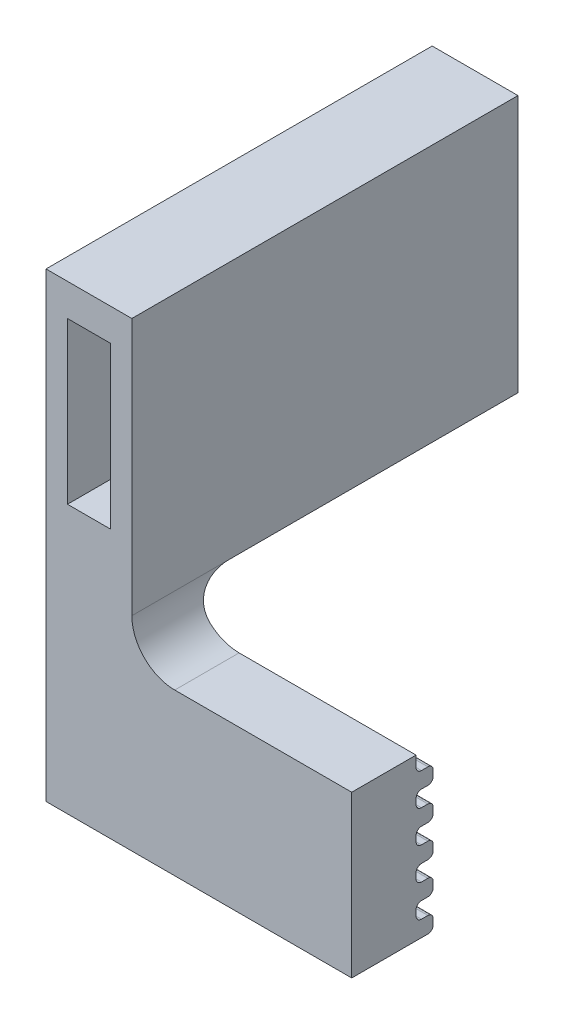
SolidWorks part; units mm, degrees
ref_plane "Спереди" through (0, 0, 0) normal (0, 0, 1) x (1, 0, 0)
ref_plane "Сверху" through (0, 0, 0) normal (0, 1, 0) x (1, 0, 0)
ref_plane "Справа" through (0, 0, 0) normal (1, 0, 0) x (0, 0, -1)
other "Configuration Table"
sketch "Эскиз1" plane through (0, 0, 0) normal (0, 0, 1) x (1, 0, 0)
  line L0 (4, 24) -> (4, 6) construction
  line L1 (2, 21) -> (6, 21)
  line L6 (2, 21) -> (2, 6)
  line L7 (2, 6) -> (6, 6)
  line L8 (6, 21) -> (6, 6)
  line L9 (0, 24) -> (8, 24)
  line L10 (0, 24) -> (0, 6)
  line L11 (0, 6) -> (8, 6)
  line L12 (8, 24) -> (8, 6)
  line L17 (8, 6) -> (8, 0)
  line L18 (0, 0) -> (0, 6)
  line L19 (0, 0) -> (8, 0)
  dimension "D1" = 4
  dimension "D3" = 0
  dimension "D4" = 8
  dimension "D5" = 6
  dimension "D6" = 15
  dimension "D7" = 3
extrude "Бобышка-Вытянуть1" add sketch "Эскиз1" along normal blind 8 contours L11 | L9 L0 L1 L8 L7 L12 | L0 L9 L10 L11 L7 L6 L1 | L17 region at (6.7143, 16.0714, 0) region at (1.2857, 16.0714, 0) region at (4, 3, 0)
extrude "Бобышка-Вытянуть2" add sketch "Эскиз1<3>" against normal blind 28 contours L9 L0 L1 L8 L7 L12 | L0 L9 L10 L11 L7 L6 L1 | L17 L11 region at (6.7143, 16.0714, 0) region at (1.2857, 16.0714, 0) region at (4, 3, 0)
sketch "Эскиз1<3>" plane through (0, 0, 0) normal (0, 0, 1) x (1, 0, 0) same geometry as "Эскиз1"
sketch "Эскиз3" plane through (0, 0, 0) normal (0, -1, 0) x (1, 0, 0)
  line L0 (5, -10) -> (-1, -10) construction
  line L1 (5, -11.5) -> (-1, -11.5)
  line L2 (5, -8.5) -> (-1, -8.5)
  line L3 (8, -10) -> (-27.6495, -10) construction
  line L4 (8, 8) -> (8, -28) construction
  line L6 (8, -6) -> (-4, -6)
  line L7 (8, -6) -> (8, -14)
  line L8 (8, -14) -> (-4, -14)
  line L9 (-4, -6) -> (-4, -14)
  arc A0 (5, -11.5) -> (5, -8.5) centre (5, -10) ccw
  arc A1 (-1, -8.5) -> (-1, -11.5) centre (-1, -10) ccw
  point P2 (2, -10)
  line M11 (0, 8) -> (0, -28)
  dimension "D1" = 3
  dimension "D2" = 6
  dimension "D3" = 3
  dimension "D4" = 8
  dimension "D5" = 12
extrude "Бобышка-Вытянуть4" add sketch "Эскиз3" against normal blind 6 contours A1 L2 L6 L9 L8 L1 M11 region at (-0.0894, 0, -12.75)
extrude "Вырез-Вытянуть2" cut sketch "Эскиз3<3>" against normal blind 6 contours L2 A1 L1 M11 | L1 A0 L2 M11 region at (3.0981, 0, -10) region at (-1.1148, 0, -10)
sketch "Эскиз3<3>" plane through (0, 0, 0) normal (0, -1, 0) x (1, 0, 0) same geometry as "Эскиз3"
sketch "Эскиз4" plane through (0, 0, 8) normal (0, 0, 1) x (1, 0, 0)
  line L1 (0, 0) -> (8, 0)
  line L2 (0, 0) -> (0, -4)
  line L3 (0, -4) -> (8, -4)
  line L4 (8, 0) -> (8, -4)
  line L5 (0, -4) -> (28.5, -4)
  line L6 (0, -4) -> (0, -19)
  line L7 (0, -19) -> (28.5, -19)
  line L8 (28.5, -4) -> (28.5, -19)
  line M16 (0, 0) -> (8, 0)
  dimension "D1" = 28.5
  dimension "D2" = 4
  dimension "D3" = 15
extrude "Бобышка-Вытянуть5" add sketch "Эскиз4" against normal blind 6 contours L8 L5 L3 L6 L7 | L4 L2 L3 M16 region at (4, -2, 8) region at (14.25, -11.5, 8)
fillet "Скругление1" radius 2 4 edges at (0, 3, -14) (-4, 3, -14) (-4, 3, -6) (0, 3, -6)
fillet "Скругление2" radius 3 1 edges at (4, 0, 2)
fillet "Скругление3" radius 4 1 edges at (8, -4, 5)
sketch "Эскиз6" plane through (28.5, 0, 0) normal (1, 0, 0) x (0, 0, -1)
  line L0 (-2, -16) -> (-2, -14.5)
  line L1 (-2, -19) -> (-0.4, -19)
  line L2 (-2, -19) -> (-2, -17.5)
  line L3 (-2, -17.5) -> (-0.4, -17.5)
  line L4 (-0.4, -19) -> (-0.4, -17.5)
  line L5 (-2, -16) -> (-0.4, -16)
  line L6 (-0.4, -16) -> (-0.4, -14.5)
  line L7 (-2, -14.5) -> (-0.4, -14.5)
  line L8 (-2, -13) -> (-2, -11.5)
  line L9 (-2, -13) -> (-0.4, -13)
  line L10 (-0.4, -13) -> (-0.4, -11.5)
  line L11 (-2, -11.5) -> (-0.4, -11.5)
  line L12 (-2, -10) -> (-2, -8.5)
  line L13 (-2, -10) -> (-0.4, -10)
  line L14 (-0.4, -10) -> (-0.4, -8.5)
  line L15 (-2, -8.5) -> (-0.4, -8.5)
  line L16 (-2, -7) -> (-2, -5.5)
  line L17 (-2, -7) -> (-0.4, -7)
  line L18 (-0.4, -7) -> (-0.4, -5.5)
  line L19 (-2, -5.5) -> (-0.4, -5.5)
  dimension "D1" = 1.5
  dimension "D2" = 1.6
  dimension "D3" = 5
extrude "Бобышка-Вытянуть7" add sketch "Эскиз6" against normal up to surface (28.5 mm away) up to face at (0, 2.4324, -7.4137)
fillet "Скругление5" radius 0.5 19 edges at (14.25, -8.5, 0.4) (14.25, -5.5, 0.4) (14.25, -5.5, 2) (14.25, -8.5, 2) (14.25, -11.5, 2) (14.25, -14.5, 2) (14.25, -7, 0.4) (14.25, -7, 2) (14.25, -10, 0.4) (14.25, -10, 2) (14.25, -13, 0.4) (14.25, -13, 2) (14.25, -14.5, 0.4) (14.25, -16, 0.4) (14.25, -16, 2) (14.25, -17.5, 2) (14.25, -17.5, 0.4) (14.25, -19, 0.4) (14.25, -11.5, 0.4)
sketch "Эскиз7" [suppressed] plane through (28.5, 0, 0) normal (1, 0, 0) x (0, 0, -1)
  line L0 (-2, -7) -> (-2, -8.5)
  line L1 (-2, -4) -> (-0.4, -4)
  line L2 (-2, -4) -> (-2, -5.5)
  line L3 (-2, -5.5) -> (-0.4, -5.5)
  line L4 (-0.4, -4) -> (-0.4, -5.5)
  line L5 (-2, -7) -> (-0.4, -7)
  line L6 (-0.4, -7) -> (-0.4, -8.5)
  line L7 (-2, -8.5) -> (-0.4, -8.5)
  line L8 (-2, -10) -> (-2, -11.5)
  line L9 (-2, -10) -> (-0.4, -10)
  line L10 (-0.4, -10) -> (-0.4, -11.5)
  line L11 (-2, -11.5) -> (-0.4, -11.5)
  line L12 (-2, -13) -> (-2, -14.5)
  line L13 (-2, -13) -> (-0.4, -13)
  line L14 (-0.4, -13) -> (-0.4, -14.5)
  line L15 (-2, -14.5) -> (-0.4, -14.5)
  line L16 (-2, -16) -> (-2, -17.5)
  line L17 (-2, -16) -> (-0.4, -16)
  line L18 (-0.4, -16) -> (-0.4, -17.5)
  line L19 (-2, -17.5) -> (-0.4, -17.5)
  dimension "D1" = 1.6
  dimension "D2" = 1.5
  dimension "D3" = 5
extrude "Бобышка-Вытянуть8" [suppressed] add sketch "Эскиз7" against normal up to surface (28.5 mm away)
fillet "Скругление6" [suppressed] radius 0.5
